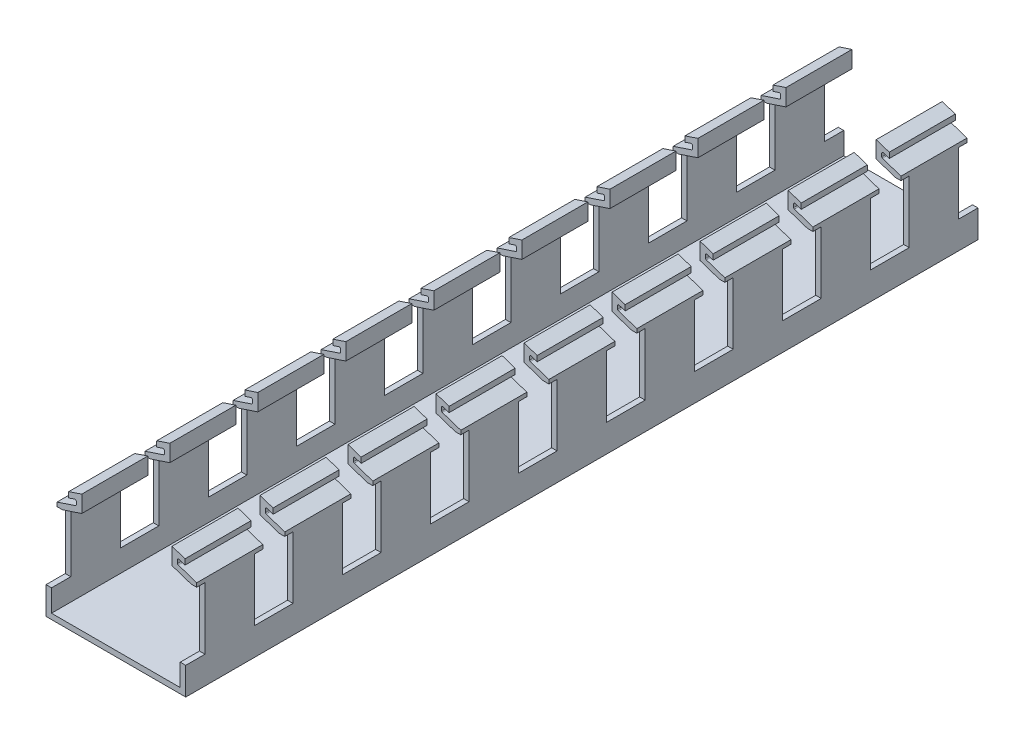
SolidWorks part; units mm, degrees
ref_plane "Alzado" through (0, 0, 0) normal (0, 0, 1) x (1, 0, 0)
ref_plane "Planta" through (0, 0, 0) normal (0, 1, 0) x (1, 0, 0)
ref_plane "Vista lateral" through (0, 0, 0) normal (1, 0, 0) x (0, 0, -1)
sketch "Croquis2" plane through (0, 0, 0) normal (0, 0, 1) x (1, 0, 0)
  line L0 (-12.7, 0) -> (12.7, 0)
  line L1 (0, 0) -> (0, 14.1113) construction
  line L2 (-12.7, 0) -> (-12.7, 17)
  line L4 (8.2, 17.4459) -> (11.7, 16.2792)
  line L5 (8.2, 20.5) -> (8.2, 17.4459)
  line L6 (10.5717, 19.7094) -> (8.2, 20.5)
  line L7 (10.5717, 18.7094) -> (10.5717, 19.7094)
  line L8 (9.2, 18.8892) -> (9.2, 18.3108)
  line L9 (10.5717, 18.7094) -> (9.4632, 19.0789)
  line L10 (-9.3368, 18.1211) -> (-12.7, 17)
  line L11 (-10.5717, 18.7094) -> (-9.4632, 19.0789)
  line L12 (-9.2, 18.8892) -> (-9.2, 18.3108)
  line L13 (9.3368, 18.1211) -> (12.7, 17)
  line L14 (12.7, 0) -> (12.7, 17)
  line L15 (11.7, 16.2792) -> (11.7, 1)
  line L16 (-10.5717, 18.7094) -> (-10.5717, 19.7094)
  line L18 (-10.5717, 19.7094) -> (-8.2, 20.5)
  line L19 (-8.2, 20.5) -> (-8.2, 17.4459)
  line L20 (-8.2, 17.4459) -> (-11.7, 16.2792)
  line L21 (-11.7, 16.2792) -> (-11.7, 1)
  line L22 (-11.7, 1) -> (11.7, 1)
  arc A0 (9.3368, 18.1211) -> (9.2, 18.3108) centre (9.4, 18.3108) cw
  arc A1 (9.2, 18.8892) -> (9.4632, 19.0789) centre (9.4, 18.8892) cw
  arc A4 (-9.2, 18.8892) -> (-9.4632, 19.0789) centre (-9.4, 18.8892) ccw
  arc A5 (-9.3368, 18.1211) -> (-9.2, 18.3108) centre (-9.4, 18.3108) ccw
  dimension "D8" = 0.2
  dimension "D1" = 25.4
  dimension "D2" = 1
  dimension "D3" = 1
  dimension "D4" = 1
  dimension "D5" = 1
  dimension "D6" = 1
  dimension "D7" = 20.5
  dimension "D9" = 8.2
  dimension "D10" = 2.5
  dimension "D11" = 71.565
  dimension "D12" = 3.0541
extrude "Saliente-Extruir1" add sketch "Croquis2" along normal mid plane 16
sketch "Croquis3" plane through (0, 0, 0) normal (1, 0, 0) x (0, 0, -1)
  line L0 (0, 0) -> (0, 24.3686) construction
  line L1 (-8, 0) -> (8, 0) construction
  line L2 (-8, 5) -> (-4.5, 5)
  line L3 (-8, 0) -> (-8, 17) construction
  line L4 (-4.5, 5) -> (-4.5, 16.2792)
  line L5 (-4.5, 16.2792) -> (-6, 16.2792)
  line L6 (-6, 16.2792) -> (-6, 20.5)
  line L7 (-8, 5) -> (-8, 20.5)
  line L8 (-8, 20.5) -> (-6, 20.5)
  line L10 (-8, 20.5) -> (8, 20.5) construction
  line L11 (8, 20.5) -> (6, 20.5)
  line L12 (8, 5) -> (8, 20.5)
  line L13 (6, 16.2792) -> (6, 20.5)
  line L14 (4.5, 16.2792) -> (6, 16.2792)
  line L15 (4.5, 5) -> (4.5, 16.2792)
  line L16 (8, 5) -> (4.5, 5)
  line L17 (-8, 16.2792) -> (8, 16.2792) construction
  dimension "D1" = 5
  dimension "D2" = 3.5
  dimension "D3" = 2
extrude "Cortar-Extruir1" cut sketch "Croquis3" against normal mid plane 66
pattern_linear "MatrizL1" count 9 spacing 16 along (0, 0, -1) of "Saliente-Extruir1", "Cortar-Extruir1"
